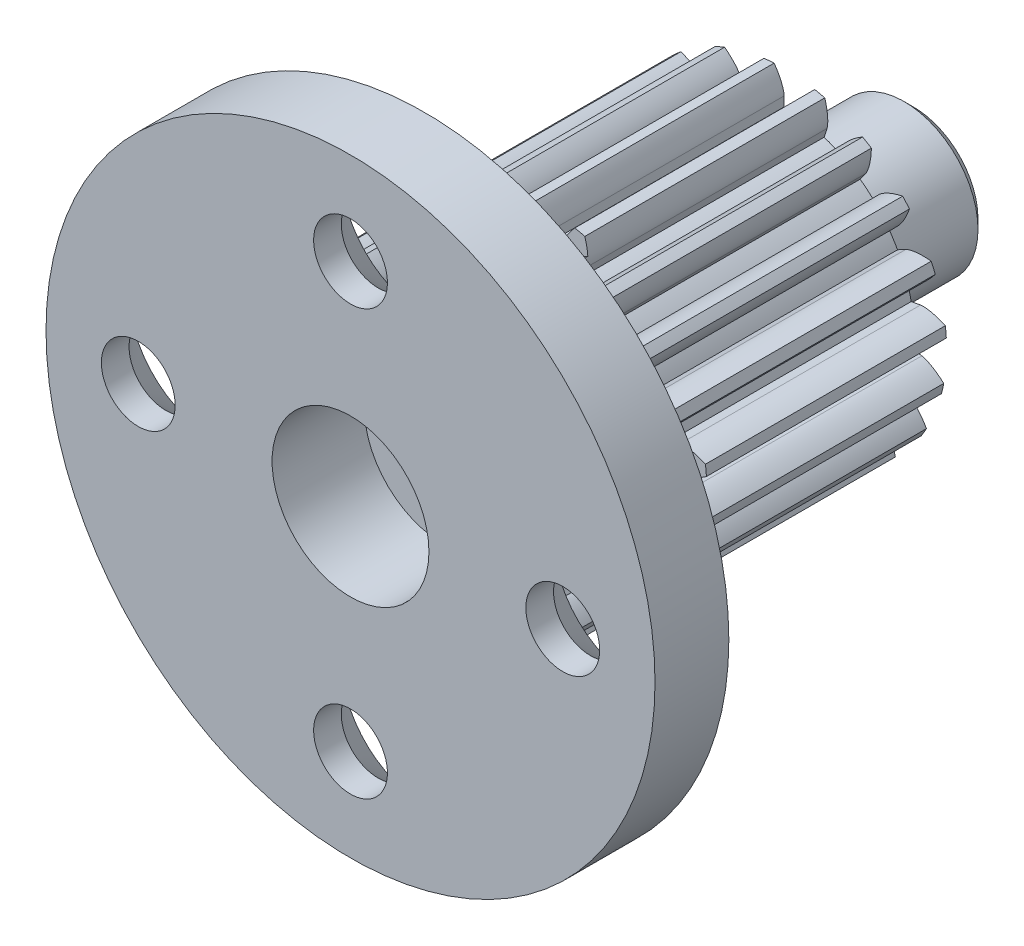
SolidWorks part; units mm, degrees
ref_plane "Front Plane" through (0, 0, 0) normal (0, 0, 1) x (1, 0, 0)
ref_plane "Top Plane" through (0, 0, 0) normal (0, 1, 0) x (1, 0, 0)
ref_plane "Right Plane" through (0, 0, 0) normal (1, 0, 0) x (0, 0, -1)
sketch "Sketch1" plane through (0, 0, 0) normal (0, 0, 1) x (1, 0, 0)
  circle A0 centre (0, 0) radius 8.8
  dimension "D1" = 17.6
extrude "Boss-Extrude1" add sketch "Sketch1" along normal mid plane 19.5
sketch "Sketch2" plane through (0, 0, 0) normal (0, 0, 1) x (1, 0, 0)
  line L0 (0, 0) -> (7.5175, 0) construction
  line L1 (0, 0) -> (7.9838, -0.5087) construction
  line L2 (0, 0) -> (7.4567, -0.9542) construction
  line L3 (7.5175, 0) -> (7, 0)
  line L4 (7.4567, -0.9542) -> (6.9434, -0.8885)
  circle A0 centre (0, 0) radius 8 construction
  circle A1 centre (0, 0) radius 7.5175 construction
  circle A2 centre (0, 0) radius 7
  circle A3 centre (0, 0) radius 8.8 construction
  circle A4 centre (0, 0) radius 8.8
  spline S0 degree 4 poles (7.5175, 0) (7.5201, 0) (7.5273, 0.0003) (7.5496, 0.0017) (7.5933, 0.0065) (7.6472, 0.0155) (7.7088, 0.0287) (7.7679, 0.0436) (7.8183, 0.0577) (7.8683, 0.0731) (7.9179, 0.0896) (7.9778, 0.1109) (8.0492, 0.1383) (8.1321, 0.173) (8.2253, 0.2156) (8.3193, 0.2624) (8.4112, 0.3112) (8.503, 0.3637) (8.5911, 0.4167) (8.6816, 0.4749) (8.7646, 0.5303) (8.8563, 0.5958) (8.93, 0.6497) (9.0257, 0.7244) (9.0818, 0.7697) (9.147, 0.8238) (9.1756, 0.8486) (9.1933, 0.8638) knots 0 0 0 0 0 0.005377 0.015084 0.04661 0.092111 0.119476 0.146842 0.174209 0.201575 0.228941 0.256307 0.307035 0.361767 0.4165 0.471232 0.525964 0.580697 0.635429 0.690161 0.744894 0.799626 0.854358 0.909091 0.954545 1 1 1 1 1 construction
  spline S1 degree 4 poles (7.5175, 0) (7.5201, 0) (7.5273, 0.0003) (7.5496, 0.0017) (7.5933, 0.0065) (7.6472, 0.0155) (7.7088, 0.0287) (7.7679, 0.0436) (7.8183, 0.0577) (7.8683, 0.0731) (7.9179, 0.0896) (7.9778, 0.1109) (8.0492, 0.1383) (8.1321, 0.173) (8.2253, 0.2156) (8.3193, 0.2624) (8.4112, 0.3112) (8.503, 0.3637) (8.5911, 0.4167) (8.6816, 0.4749) (8.7646, 0.5303) (8.8563, 0.5958) (8.93, 0.6497) (9.005, 0.7082) (9.0413, 0.7371) (9.0598, 0.7521) knots 0 0 0 0 0 0.005377 0.015084 0.04661 0.092111 0.119476 0.146842 0.174209 0.201575 0.228941 0.256307 0.307035 0.361767 0.4165 0.471232 0.525964 0.580697 0.635429 0.690161 0.744894 0.799626 0.854358 0.909091 0.909091 0.909091 0.909091 0.909091
  spline S2 degree 4 poles (7.4567, -0.9542) (7.4593, -0.9545) (7.4664, -0.9557) (7.4883, -0.9599) (7.5311, -0.9703) (7.5833, -0.986) (7.6428, -1.0069) (7.6995, -1.0292) (7.7477, -1.0496) (7.7954, -1.0712) (7.8425, -1.0938) (7.8992, -1.1226) (7.9666, -1.1588) (8.0443, -1.2038) (8.1314, -1.2579) (8.2188, -1.3162) (8.3036, -1.3763) (8.388, -1.44) (8.4688, -1.5037) (8.5511, -1.573) (8.6264, -1.6384) (8.7091, -1.7151) (8.7753, -1.7779) (8.8608, -1.8642) (8.9107, -1.9162) (8.9684, -1.9782) (8.9937, -2.0064) (9.0093, -2.0237) knots 0 0 0 0 0 0.005377 0.015084 0.04661 0.092111 0.119476 0.146842 0.174209 0.201575 0.228941 0.256307 0.307035 0.361767 0.4165 0.471232 0.525964 0.580697 0.635429 0.690161 0.744894 0.799626 0.854358 0.909091 0.954545 1 1 1 1 1 construction
  spline S3 degree 4 poles (7.4567, -0.9542) (7.4593, -0.9545) (7.4664, -0.9557) (7.4883, -0.9599) (7.5311, -0.9703) (7.5833, -0.986) (7.6428, -1.0069) (7.6995, -1.0292) (7.7477, -1.0496) (7.7954, -1.0712) (7.8425, -1.0938) (7.8992, -1.1226) (7.9666, -1.1588) (8.0443, -1.2038) (8.1314, -1.2579) (8.2188, -1.3162) (8.3036, -1.3763) (8.388, -1.44) (8.4688, -1.5037) (8.5511, -1.573) (8.6264, -1.6384) (8.7091, -1.7151) (8.7753, -1.7779) (8.8422, -1.8455) (8.8746, -1.8788) (8.891, -1.8959) knots 0 0 0 0 0 0.005377 0.015084 0.04661 0.092111 0.119476 0.146842 0.174209 0.201575 0.228941 0.256307 0.307035 0.361767 0.4165 0.471232 0.525964 0.580697 0.635429 0.690161 0.744894 0.799626 0.854358 0.909091 0.909091 0.909091 0.909091 0.909091
  dimension "D1" = 16
  dimension "D2" = 15.0351
  dimension "D3" = 14
  dimension "D4" = 3.646
  dimension "D5" = 3.646
extrude "Cut-Extrude1" cut sketch "Sketch2" against normal through all both and the other way through all contours A2 S3 A4 S1 region at (8.0236, -0.5113, 0)
pattern_circular "CirPattern2" count 20 over 360 about axis through (0, 0, -9.75) along (0, 0, 1) of "Cut-Extrude1"
sketch "Sketch3" plane through (0, 0, 0) normal (0, 1, 0) x (1, 0, 0)
  line L0 (0, 9.75) -> (0, 20.841) construction
  line L1 (0, 20.841) -> (0, -26.4333) construction
  line L2 (0, 16.75) -> (-4, 16.75)
  line L3 (-4, 16.75) -> (-4, 11.25)
  line L4 (-4, 11.25) -> (-4.5, 11.25)
  line L6 (-4.5, 11.25) -> (-4.5, 9.75)
  line L9 (0, 9.75) -> (-4.5, 9.75)
  line L10 (-0.544, -9.75) -> (0, -9.75) construction
  line L11 (0, -9.75) -> (-16.5, -9.75)
  line L12 (-16.5, -9.75) -> (-16.5, -13.75)
  line L13 (-16.5, -13.75) -> (0, -13.75)
  line L14 (0, 16.75) -> (0, -13.75)
  line L15 (0, 9.75) -> (-0.544, 9.75) construction
  point P7 (0, -9.75)
  point P14 (0, 9.75)
  dimension "D1" = 4
  dimension "D2" = 5.5
  dimension "D3" = 1.5
  dimension "D4" = 0.5
  dimension "D5" = 4
  dimension "D6" = 16.5
revolve "Revolve1" add sketch "Sketch3" angle 360 about L0 region at (-2.0587, 0, -13.1783) region at (-8.25, 0, 11.75)
chamfer "Chamfer1" distance 0.5 angle 45 1 edges at (4.5, 0, -9.75)
chamfer "Chamfer2" distance 0.5 angle 45 1 edges at (4, 0, -16.75)
sketch "Sketch4" plane through (0, 0, 13.75) normal (0, 0, 1) x (1, 0, 0)
  circle A0 centre (0, 0) radius 2.5
  dimension "D1" = 5
extrude "Cut-Extrude2" cut sketch "Sketch4" against normal through all
sketch "Sketch5" plane through (0, 0, 13.75) normal (0, 0, 1) x (1, 0, 0)
  circle A0 centre (0, 0) radius 4.25
  dimension "D1" = 8.5
extrude "Cut-Extrude3" cut sketch "Sketch5" against normal blind 5
sketch "Sketch6" plane through (0, 0, 9.75) normal (0, 0, -1) x (-1, 0, 0)
  circle A0 centre (0, 0) radius 11.5 construction
  circle A1 centre (0, 11.5) radius 2
  circle A2 centre (11.5, 0) radius 2
  circle A3 centre (0, -11.5) radius 2
  circle A4 centre (-11.5, 0) radius 2
  point P14 (0, 0)
  dimension "D1" = 23
  dimension "D2" = 4
  dimension "D3" = 4
extrude "Cut-Extrude4" cut sketch "Sketch6" against normal through all
sketch "Sketch7" plane through (0, 0, 0) normal (0, 1, 0) x (1, 0, 0)
  line L0 (9.5, -13.75) -> (13.5, -13.75) construction
  line L1 (13.5, -9.75) -> (9.5, -9.75) construction
  line L2 (9.5, -13.75) -> (13.5, -13.75)
  line L4 (11.5, -9.75) -> (11.5, -13.75) construction
  line L5 (11.5, -9.75) -> (16, -9.75)
  line L6 (16, -9.75) -> (13.5, -12.25)
  line L7 (13.5, -12.25) -> (11.5, -12.25)
  line L8 (11.5, -9.75) -> (11.5, -12.25)
  dimension "D2" = 4.5
  dimension "D3" = 2
  dimension "D1" = 2.5
revolve "Cut-Revolve1" cut sketch "Sketch7" angle 360 about L4 region at (13.2051, 0, 10.8397)
pattern_circular "CirPattern3" count 4 over 360 about axis through (0, 0, -16.75) along (0, 0, 1) of "Cut-Revolve1"
sketch "Sketch8" plane through (0, 0, 9.75) normal (0, 0, -1) x (-1, 0, 0)
  line L0 (0, 11.5) -> (0, 0) construction
  circle A0 centre (0, 11.5) radius 4.5
  circle A1 centre (0, 0) radius 11.5 construction
  circle A2 centre (11.5, 0) radius 4.5
  circle A3 centre (0, -11.5) radius 4.5
  circle A4 centre (-11.5, 0) radius 4.5
  point P14 (0, 0)
  dimension "D1" = 23
  dimension "D2" = 9
extrude "Cut-Extrude5" cut sketch "Sketch8" along normal blind 6.5
equation "\"Ns\"= 20"
equation "\"module\"= 0.8"
equation "\"pressure angle\"= 20deg"
equation "\"h_a\"= 1 * \"module\"'addendum"
equation "\"h_b\"= 1.25 * \"module\"'dedendum"
equation "\"clr_tip_root\"= \"h_f\" - \"h_a\"'clearance of gear tooth tip and root"
equation "\"dp_s\"= \"module\" * \"Ns\"'PCD"
equation "\"db_s\"= \"dp_s\" * cos ( \"pressure angle\" )'base CD"
equation "\"D1@Sketch1\"=\"dp_s\" + 2*\"h_a\""
equation "\"fw_s_calc\"= 13mm'face width"
equation "\"D1@Boss-Extrude1\"=\"fw_s_used\""
equation "\"D1@Sketch2\"=\"dp_s\""
equation "\"D2@Sketch2\"= \"db_s\""
equation "\"D3@Sketch2\"=\"dp_s\"- 2*\"h_b\""
equation "\"alpha_s\"= sqr ( \"dp_s\" ^ 2 - \"db_s\" ^ 2 ) / \"db_s\" * 180 / pi - \"pressure angle\""
equation "\"D4@Sketch2\"= 360 / ( 4 * \"Ns\" ) - \"alpha_s\""
equation "\"beta_s\"= ( 360 / ( 4 * \"Ns\" ) - \"alpha_s\" ) * 2"
equation "\"D5@Sketch2\"= 360 / ( 4 * \"Ns\" ) - \"alpha_s\""
equation "\"D1@CirPattern2\"=\"Ns\""
equation "\"Np\"= 40"
equation "\"dp_p\"= \"module\" * \"Np\"'PCD"
equation "\"db_p\"= \"dp_p\" * cos ( \"pressure angle\" )'base CD"
equation "\"fw_p\"= \"fw_r\""
equation "\"alpha_p\"= sqr ( \"dp_p\" ^ 2 - \"db_p\" ^ 2 ) / \"db_p\" * 180 / pi - \"pressure angle\""
equation "\"beta_p\"= ( 360 / ( 4 * \"Np\" ) - \"alpha_p\" ) * 2"
equation "\"Nr\"= \"Ns\" + 2 * \"Np\"'num teeth"
equation "\"pressure_angle\"= 20deg"
equation "\"h_f\"= 1.25 * \"module\"'dedendum"
equation "\"dp_r\"= \"module\" * \"Nr\"'PCD"
equation "\"db_r\"= \"dp_r\" * cos ( \"pressure_angle\" )'base CD"
equation "\"fw_r\"= 11.5mm'face width"
equation "\"alpha_r\"= sqr ( \"dp_r\" ^ 2 - \"db_r\" ^ 2 ) / \"db_r\" * 180 / pi - \"pressure_angle\""
equation "\"beta_r\"= ( 360 / ( 4 * \"Nr\" ) + \"alpha_r\" ) * 2"
equation "\"bearing_ID\"= \"module\" * ( \"Ns\" + \"Np\" ) + 10"
equation "\"bearing_OD\"= 1.18 * \"bearing_ID\" + 8.57"
equation "\"bearing_height\"= 0.09 * \"bearing_ID\" + 4.62"
equation "\"clearance_planet\"=1.5"
equation "\"case_dist\"= \"sec_carrier_thickness\" + \"clearance_planet\" + \"sun_coupler_hub_thickness\" - \"case_mounting_surface_height\""
equation "\"Motor_case_OD_max\"= \"case_mounting_PCD\" + \"case_mounting_hole_allen_socket_dia\" + \"clearance_case_mount_holes_shell_thickness\" * 2"
equation "\"case_mounting_PCD\"= \"motor_case_OD_base\" + \"case_mounting_hole_shift\" * 2"
equation "\"bearing mount thickness\"= IIF((\"bearing_OD\" + \"output_mounting_hole_dia\" * 4) > (\"Nr\" * \"module\" + 2 * \"h_b\"), \"output_mounting_hole_dia\" * 2, ((\"Nr\" * \"module\" + 2 * \"h_b\" - (\"bearing_OD\" + \"output_mounting_hole_dia\" * 4)) / 2) + \"output_mounting_hole_dia\" * 2 + \"standard_clearance_1_5mm\")"
equation "\"case_mounting_hole_dia\"=3"
equation "\"output_mounting_PCD\"= \"bearing_OD\" + \"bearing mount thickness\""
equation "\"output_mounting_hole_dia\"= 4"
equation "\"clearance_case_mount_holes_shell_thickness\"= 1"
equation "\"motor_case_OD_base\"= \"motor_OD\" + \"clearance_motor_and_case\" * 2 + \"Motor_case_thickness\" * 2"
equation "\"sec_carrier_thickness\"= 5"
equation "\"sun_coupler_hub_thickness\"= 4"
equation "\"clearance_sun_coupler_sec_carrier\"= 1.5"
equation "\"clearance_motor_and_case\" = IIF(\"ring_OD\" < \"motor_OD\", 5, (\"ring_OD\" - \"motor_OD\")/2 + 5)"
equation "\"motor_OD\"= 88.6"
equation "\"Motor_case_thickness\"= 2.5"
equation "\"Motor_case_ID\"= \"motor_OD\" + \"clearance_motor_and_case\" * 2"
equation "\"case_mounting_hole_shift\"= \"case_mounting_hole_dia\" / 2 - 0.5"
equation "\"output_mounting_nut_wrench_size\"= 7"
equation "\"output_mounting_nut_thickness\"= 3.2"
equation "\"case_mounting_hole_allen_socket_dia\"= 5.5"
equation "\"output_mounting_nut_depth\"= 3"
equation "\"case_mounting_bolt_depth\"= 4.5"
equation "\"ring_radial_thickness\"= 5"
equation "\"ring_OD\"= \"Nr\" * \"module\" + \"ring_radial_thickness\" * 2"
equation "\"ring_to_chamfer_clearance\"= 2"
equation "\"Motor_case_OD_base_to_chamfer\"=5"
equation "\"pattern_offset_from_motor_case_OD_base\"= 3"
equation "\"pattern_bulge_dia\"= 3"
equation "\"pattern_num_bulge\"= 18"
equation "\"pattern_depth\"= 2"
equation "\"motor_height\"= 43"
equation "\"case_mounting_wrench_size\"= 5.5"
equation "\"case_mounting_nut_clearance\"= 2"
equation "\"base_plate_thickness\"= 4"
equation "\"case_mounting_nut_thickness\"= 2.4"
equation "\"case_mounting_surface_height\"= 4"
equation "\"motor_mount_hole_PCD\"= 32"
equation "\"motor_mount_hole_dia\"= 4"
equation "\"motor_mount_hole_num\"= 4"
equation "\"central_hole_offset_from_motor_mount_PCD\"= 5"
equation "\"wire_slot_dist_from_center\"= 30"
equation "\"wire_slot_length\"= 10"
equation "\"wire_slot_radius\"= 4"
equation "\"driver_upper_holes_dist_from_center\"= 23"
equation "\"driver_lower_holes_dist_from_center\"= 15"
equation "\"driver_side_holes_dist_from_center\"= 20"
equation "\"driver_mount_holes_dia\"= 2.5"
equation "\"driver_mount_inserts_OD\"= 3.5"
equation "\"driver_mount_thickness\"= 1.5"
equation "\"driver_mount_height\"= 4"
equation "\"air_flow_hole_offset\"= 3"
equation "\"num_planet\"= 3"
equation "\"planet_pin_bolt_dia\"= 5"
equation "\"planet_pin_socket_head_dia\"= 8.5"
equation "\"carrier_PCD\"= ( \"Np\" + \"Ns\" ) * \"module\""
equation "\"planet_shaft_dia\"= 8"
equation "\"planet_shaft_step_offset\"= 1"
equation "\"carrier_trapezoidal_support_sun_offset\"= 5"
equation "\"carrier_trapezoidal_support_hole_PCD_offset_bearing_ID\"= 4"
equation "\"carrier_trapezoidal_support_hole_dia\"= 3"
equation "\"carrier_trapezoidal_support_hole_socket_head_dia\"= 5.5"
equation "\"carrier_bearing_step_width\"= 1.5"
equation "\"standard_clearance_1_5mm\"=1.5"
equation "\"standard_fillet_1_5mm\"= 1.5"
equation "\"sun_shaft_bearing_OD\"= 16"
equation "\"sun_shaft_bearing_width\"= 4"
equation "\"standard_bearing_insertion_chamfer\"= 0.5"
equation "\"carrier_trapezoidal_support_hole_wrench_size\"= 5.5"
equation "\"planet_pin_bolt_wrench_size\"= 8"
equation "\"planet_bearing_OD\"= 12"
equation "\"planet_bearing_width\"= 3"
equation "\"planet_bore\"= 10"
equation "\"motor_output_hole_PCD\"= 23"
equation "\"motor_output_hole_dia\"= 4"
equation "\"motor_output_hole_num\"= 4"
equation "\"sun_shaft_bearing_ID\"= 8"
equation "\"D1@Sketch3\"=\"sun_shaft_bearing_ID\"/2"
equation "\"D2@Sketch3\"=\"sun_shaft_bearing_width\" + \"standard_clearance_1_5mm\""
equation "\"D3@Sketch3\"=\"standard_clearance_1_5mm\""
equation "\"D4@Sketch3\"=\"standard_clearance_1_5mm\"/3"
equation "\"D5@Sketch3\"=\"sun_coupler_hub_thickness\""
equation "\"sun_hub_dia\"= \"motor_output_hole_PCD\" + \"motor_output_hole_dia\" + \"standard_clearance_1_5mm\" * 4"
equation "\"D6@Sketch3\"=\"sun_hub_dia\"/2"
equation "\"D1@Chamfer2\"=\"standard_bearing_insertion_chamfer\""
equation "\"D1@Chamfer1\"=\"standard_bearing_insertion_chamfer\""
equation "\"sun_central_bolt_dia\"= 5"
equation "\"sun_central_bolt_socket_head_dia\"= 8.5"
equation "\"D1@Sketch4\"=\"sun_central_bolt_dia\""
equation "\"D1@Cut-Extrude3\"=\"sun_central_bolt_dia\""
equation "\"D1@Sketch5\"=\"sun_central_bolt_socket_head_dia\""
equation "\"fw_s_used\"= \"fw_p\" + \"clearance_planet\" + \"sec_carrier_thickness\" + \"standard_clearance_1_5mm\""
equation "\"D1@Sketch6\"=\"motor_output_hole_PCD\""
equation "\"D2@Sketch6\"=\"motor_output_hole_dia\""
equation "\"D3@Sketch6\"=\"motor_output_hole_num\""
equation "\"motor_output_hole_CSK_OD\"= 9'8.96 is exact value"
equation "\"motor_output_hole_CSK_head_height\"= 2.5"
equation "\"D2@Sketch7\"=\"motor_output_hole_CSK_OD\"/2"
equation "\"D3@Sketch7\"=\"motor_output_hole_dia\"/2"
equation "\"D1@CirPattern3\"=\"motor_output_hole_num\""
equation "\"D1@Sketch7\"=\"motor_output_hole_CSK_head_height\""
equation "\"D1@Sketch8\"=\"motor_output_hole_PCD\""
equation "\"D2@Sketch8\"=\"motor_output_hole_CSK_OD\""
equation "\"D1@Cut-Extrude5\"=\"sec_carrier_thickness\"+\"standard_clearance_1_5mm\""
equation "\"Cut-Extrude5\"= IIF ( ( \"Ns\" * \"module\" + 2 * \"h_a\" ) < ( \"motor_output_hole_PCD\" - \"motor_output_hole_CSK_OD\" ) , \"suppressed\" , \"unsuppressed\" )"
equation "\"bearing_retainer_thickness\"= 2"
